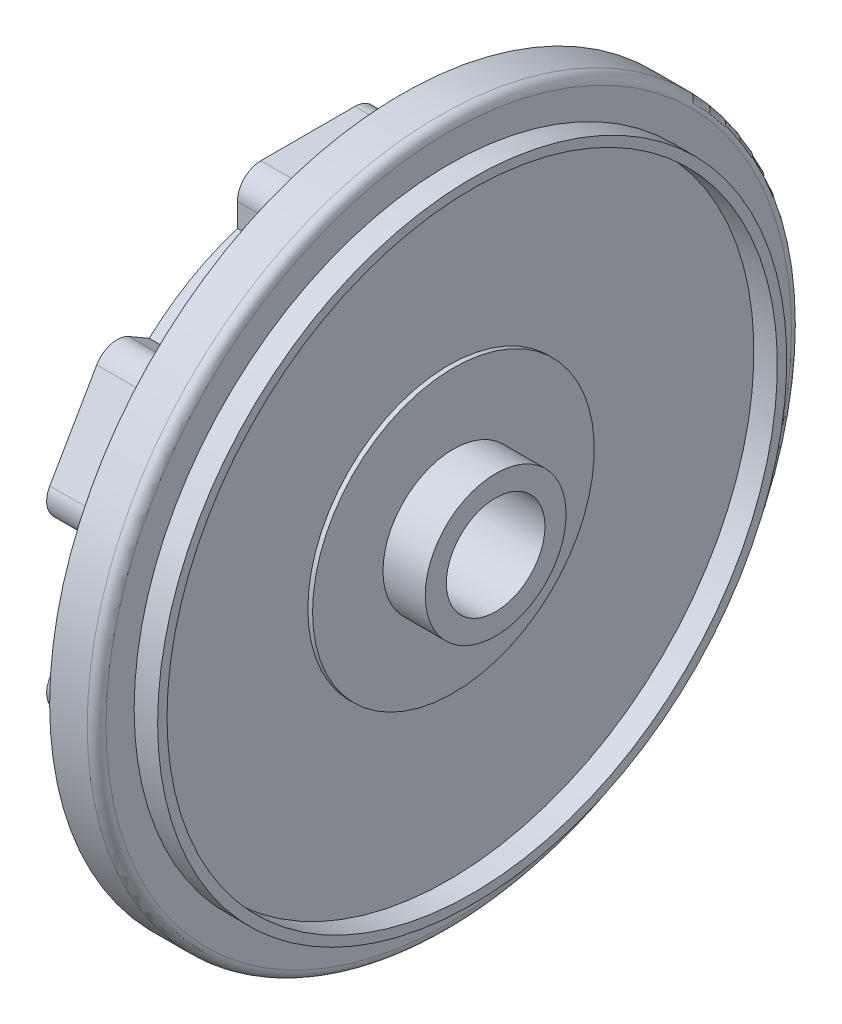
SolidWorks part; units mm, degrees
ref_plane "Front Plane" through (0, 0, 0) normal (0, 0, 1) x (1, 0, 0)
ref_plane "Top Plane" through (0, 0, 0) normal (0, 1, 0) x (1, 0, 0)
ref_plane "Right Plane" through (0, 0, 0) normal (1, 0, 0) x (0, 0, -1)
sketch "Sketch1" plane through (0, 0, 0) normal (0, 0, 1) x (1, 0, 0)
  line L0 (0, 0) -> (6, 0) construction
  line L1 (3, 1.05) -> (3, 7.5)
  line L2 (3, 7.5) -> (4, 7.5)
  line L3 (4, 7.5) -> (4, 6.7)
  line L4 (4, 6.7) -> (4.5, 6.7)
  line L5 (4.5, 6.7) -> (4.5, 6.5)
  line L6 (4.5, 6.5) -> (4, 6.5)
  line L7 (4, 6.5) -> (4, 3)
  line L8 (4, 3) -> (4.1, 3)
  line L9 (4.1, 3) -> (4.1, 1.5)
  line L10 (4.1, 1.5) -> (5, 1.5)
  line L11 (5, 1.5) -> (5, 1.05)
  line L12 (5, 1.05) -> (3, 1.05)
  point P16 (3, 0)
  dimension "D1" = 15
  dimension "D2" = 2
  dimension "D3" = 1
  dimension "D4" = 0.5
  dimension "D5" = 0.2
  dimension "D6" = 6
  dimension "D7" = 3.5
  dimension "D8" = 0.1
  dimension "D9" = 3
  dimension "D10" = 2.1
  dimension "D11" = 6
revolve "Revolve1" add sketch "Sketch1" angle 360 about L0
fillet "Fillet1" radius 0.2 1 edges at (4, 0, 7.5)
sketch "Sketch2" plane through (3, 0, 0) normal (-1, 0, 0) x (0, 0, 1)
  circle A0 centre (0, 0) radius 5
  circle A1 centre (0, 0) radius 1.05
  dimension "D1" = 10
  dimension "D2" = 2.1
extrude "Boss-Extrude1" add sketch "Sketch2" along normal blind 2
sketch "Sketch3" plane through (1, 0, 0) normal (-1, 0, 0) x (0, 0, 1)
  line L0 (0, 7.5) -> (0, -7.5) construction
  line L1 (-1, 5.7697) -> (1, 5.7697)
  line L2 (1.5, 5.2697) -> (1.5, 4.7697)
  line L3 (-1.5, 5.2697) -> (-1.5, 4.7697)
  line L4 (6.4952, 3.75) -> (-6.4952, -3.75) construction
  line L5 (6.4952, -3.75) -> (-6.4952, 3.75) construction
  line L6 (4.4967, 3.7509) -> (5.4967, 2.0188)
  line L7 (5.3137, 1.3358) -> (4.8807, 1.0858)
  line L8 (3.8137, 3.9339) -> (3.3807, 3.6839)
  line L9 (5.4967, -2.0188) -> (4.4967, -3.7509)
  line L10 (3.8137, -3.9339) -> (3.3807, -3.6839)
  line L11 (3.75, -6.4952) -> (-3.75, 6.4952) construction
  line L12 (1.5, -5.2697) -> (1.5, -4.7697)
  line L13 (5.3137, -1.3358) -> (4.8807, -1.0858)
  line L14 (-1, -5.7697) -> (1, -5.7697)
  line L15 (-1.5, -5.2697) -> (-1.5, -4.7697)
  line L16 (-3.8137, -3.9339) -> (-3.3807, -3.6839)
  line L17 (-5.4967, -2.0188) -> (-4.4967, -3.7509)
  line L18 (-5.3137, -1.3358) -> (-4.8807, -1.0858)
  line L19 (-5.3137, 1.3358) -> (-4.8807, 1.0858)
  line L20 (-4.4967, 3.7509) -> (-5.4967, 2.0188)
  line L21 (-3.8137, 3.9339) -> (-3.3807, 3.6839)
  circle A0 centre (0, 0) radius 7.5 construction
  circle A1 centre (0, 0) radius 5 construction
  circle A2 centre (0, 0) radius 5 construction
  arc A3 (-4.8807, -1.0858) -> (-3.3807, -3.6839) centre (0, 0) ccw
  arc A4 (-1.5, -4.7697) -> (1.5, -4.7697) centre (0, 0) ccw
  arc A5 (3.3807, -3.6839) -> (4.8807, -1.0858) centre (0, 0) ccw
  arc A6 (4.8807, 1.0858) -> (3.3807, 3.6839) centre (0, 0) ccw
  arc A7 (1.5, 4.7697) -> (-1.5, 4.7697) centre (0, 0) ccw
  arc A8 (-3.3807, 3.6839) -> (-4.8807, 1.0858) centre (0, 0) ccw
  arc A9 (-5.3137, 1.3358) -> (-5.4967, 2.0188) centre (-5.0637, 1.7688) cw
  arc A10 (-4.4967, 3.7509) -> (-3.8137, 3.9339) centre (-4.0637, 3.5009) cw
  arc A11 (-1.5, 5.2697) -> (-1, 5.7697) centre (-1, 5.2697) cw
  arc A12 (1, 5.7697) -> (1.5, 5.2697) centre (1, 5.2697) cw
  arc A13 (3.8137, 3.9339) -> (4.4967, 3.7509) centre (4.0637, 3.5009) cw
  arc A14 (5.4967, 2.0188) -> (5.3137, 1.3358) centre (5.0637, 1.7688) cw
  arc A15 (5.3137, -1.3358) -> (5.4967, -2.0188) centre (5.0637, -1.7688) cw
  arc A16 (4.4967, -3.7509) -> (3.8137, -3.9339) centre (4.0637, -3.5009) cw
  arc A17 (1.5, -5.2697) -> (1, -5.7697) centre (1, -5.2697) cw
  arc A18 (-1, -5.7697) -> (-1.5, -5.2697) centre (-1, -5.2697) cw
  arc A19 (-3.8137, -3.9339) -> (-4.4967, -3.7509) centre (-4.0637, -3.5009) cw
  arc A20 (-5.4967, -2.0188) -> (-5.3137, -1.3358) centre (-5.0637, -1.7688) cw
  point P12 (0, 5.7697)
  point P24 (4.9967, 2.8848)
  point P32 (4.9967, -2.8848)
  point P47 (-5.7467, 1.5858)
  point P50 (-4.2467, 4.1839)
  point P53 (-1.5, 5.7697)
  point P56 (1.5, 5.7697)
  point P59 (4.2467, 4.1839)
  point P62 (5.7467, 1.5858)
  point P65 (5.7467, -1.5858)
  point P68 (4.2467, -4.1839)
  point P71 (1.5, -5.7697)
  point P74 (-1.5, -5.7697)
  point P77 (-4.2467, -4.1839)
  point P80 (-5.7467, -1.5858)
  dimension "D8" = 0.5
  dimension "D1" = 1.5
  dimension "D2" = 1
  dimension "D3" = 60
  dimension "D4" = 60
  dimension "D5" = 1
  dimension "D6" = 1.5
  dimension "D7" = 30
  dimension "D9" = 1
  dimension "D10" = 1.5
extrude "Boss-Extrude2" add sketch "Sketch3" against normal blind 1
